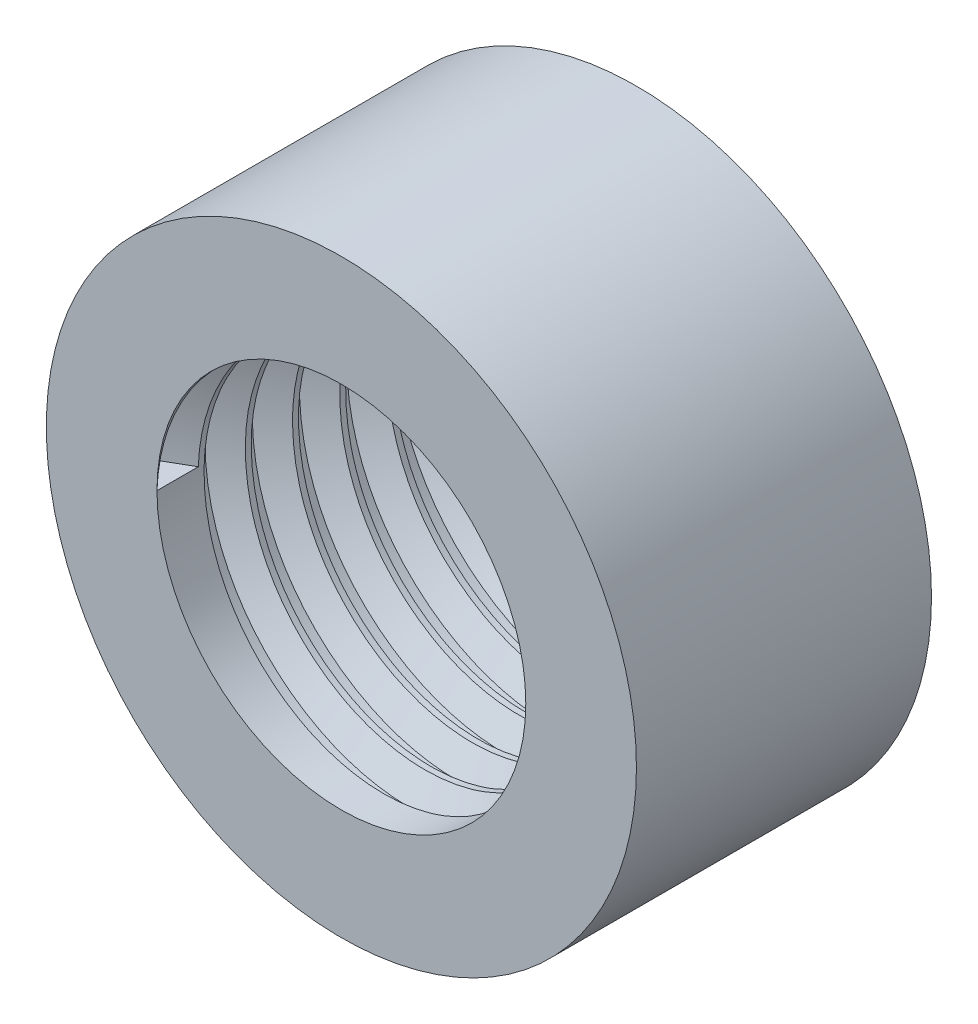
SolidWorks part; units mm, degrees
ref_plane "Front Plane" through (0, 0, 0) normal (1, 0, 0) x (0, 1, 0)
ref_plane "Top Plane" through (0, 0, 0) normal (0, 0, 1) x (0, 1, 0)
ref_plane "Right Plane" through (0, 0, 0) normal (0, 1, 0) x (-1, 0, 0)
sketch "Sketch1" plane through (0, 0, 0) normal (0, 0, 1) x (0, 1, 0)
  circle A0 centre (0, 0) radius 3.125
  circle A1 centre (0, 0) radius 5
  dimension "D1" = 6.25
  dimension "D2" = 10
extrude "Boss-Extrude1" add sketch "Sketch1" along normal blind 5
thread "Thread1" pitch 0.8 method cut profile "Thread Profile1" start angle 0, offset 0, length 0, pitch 0.8, diameter 6.25
ref_plane "Plane1" through (-3.125, 0, 5) normal (0, 1, 0) x (1, 0, 0)
sketch "Thread Profile1" plane through (-3.125, 0, 5) normal (0, 1, 0) x (1, 0, 0)
  line L0 (0, 0) -> (0, 0.8) construction
  line L11 (0, 0) -> (0, 0.7)
  line L12 (0, 0.7) -> (-0.433, 0.45)
  line L13 (-0.433, 0.45) -> (-0.433, 0.25)
  line L15 (-0.433, 0.25) -> (0, 0)
  line L17 (-0.433, 0.35) -> (0, 0.35) construction
  point P2 (0, 0)
  dimension "Pitch" = 0.8
  dimension "Profile_Angle" = 60
  dimension "Profile_Land" = 0.2
  dimension "Profile_Height" = 0.433
